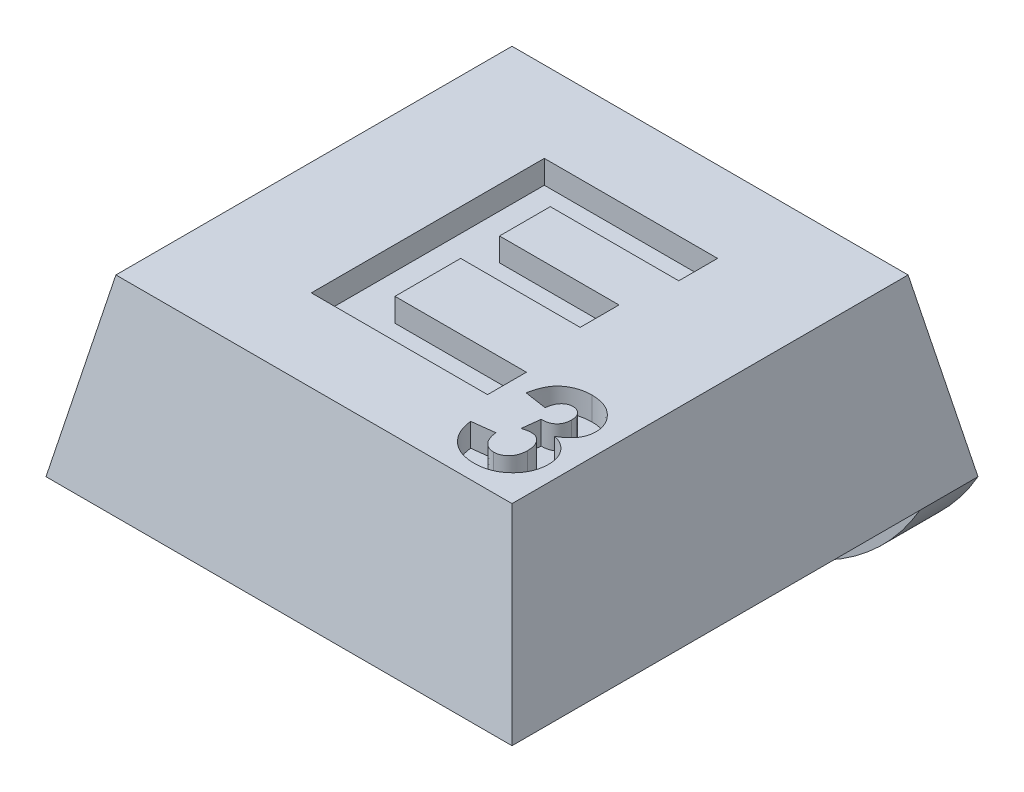
SolidWorks part; units mm, degrees
ref_plane "Front Plane" through (0, 0, 0) normal (0, 0, 1) x (1, 0, 0)
ref_plane "Top Plane" through (0, 0, 0) normal (0, 1, 0) x (1, 0, 0)
ref_plane "Right Plane" through (0, 0, 0) normal (1, 0, 0) x (0, 0, -1)
sketch "Sketch1" plane through (0, 0, 0) normal (0, 1, 0) x (1, 0, 0)
  line L1 (0, 0) -> (8, 0)
  line L2 (0, 0) -> (0, 8)
  line L3 (0, 8) -> (8, 8)
  line L4 (8, 0) -> (8, 8)
  dimension "D1" = 8
  dimension "D2" = 8
extrude "Boss-Extrude1" add sketch "Sketch1" along normal blind 3
sketch "Sketch2" plane through (0, 0, 0) normal (0, 0, 1) x (1, 0, 0)
  line L0 (0, 0) -> (0.6, 3)
  line L1 (0, 3) -> (8, 3) construction
  line L2 (0.6, 3) -> (0, 3)
  line L3 (0, 3) -> (0, 0)
  line L4 (8, 0) -> (7.4, 3)
  line L5 (7.4, 3) -> (8, 3)
  line L6 (8, 3) -> (8, 0)
  dimension "D1" = 0.6
  dimension "D2" = 0.6
extrude "Cut-Extrude1" cut sketch "Sketch2" against normal through all both and the other way through all
sketch "Sketch3" plane through (0, 0, 0) normal (1, 0, 0) x (0, 0, -1)
  line L0 (0, 0) -> (0.6, 3)
  line L1 (8, 3) -> (0, 3) construction
  line L2 (0.6, 3) -> (0, 3)
  line L3 (0, 3) -> (0, 0)
  line L4 (8, 3) -> (7.4, 3)
  line L5 (7.4, 3) -> (8, 0)
  line L6 (8, 3) -> (8, 0)
  dimension "D1" = 0.6
  dimension "D2" = 0.6
extrude "Cut-Extrude2" cut sketch "Sketch3" along normal blind 11
sketch "Sketch4" plane through (0, 0, 0) normal (0, -1, 0) x (1, 0, 0)
  line L0 (8, 0) -> (8, -8) construction
  line L3 (0, 0) -> (8, 0) construction
  circle A0 centre (4, -3.75) radius 1.8
  dimension "D1" = 3.6
  dimension "D2" = 4
  dimension "D3" = 3.75
extrude "Cut-Extrude3" cut sketch "Sketch4" against normal blind 0.8
sketch "Sketch5" plane through (0, 0, 0) normal (0, -1, 0) x (1, 0, 0)
  line L0 (8, 0) -> (8, -8) construction
  line L1 (0, -8) -> (8, -8)
  line L2 (0, -8) -> (0, -7)
  line L3 (0, -7) -> (8, -7)
  line L4 (8, -8) -> (8, -7)
  dimension "D1" = 1
extrude "Boss-Extrude2" add sketch "Sketch5" along normal blind 2
fillet "Fillet1" radius 4 2 edges at (8, -2, -7.5) (0, -2, -7.5)
sketch "Sketch6" plane through (0, 3, 0) normal (0, 1, 0) x (1, 0, 0)
  text T0 "E" font "Arial" height 4
extrude "Cut-Extrude4" cut sketch "Sketch6" against normal blind 0.4
sketch "Sketch7" plane through (0, 3, 0) normal (0, 1, 0) x (1, 0, 0)
  text T0 "3" font "Arial" height 2
extrude "Cut-Extrude5" cut sketch "Sketch7" against normal blind 0.4
